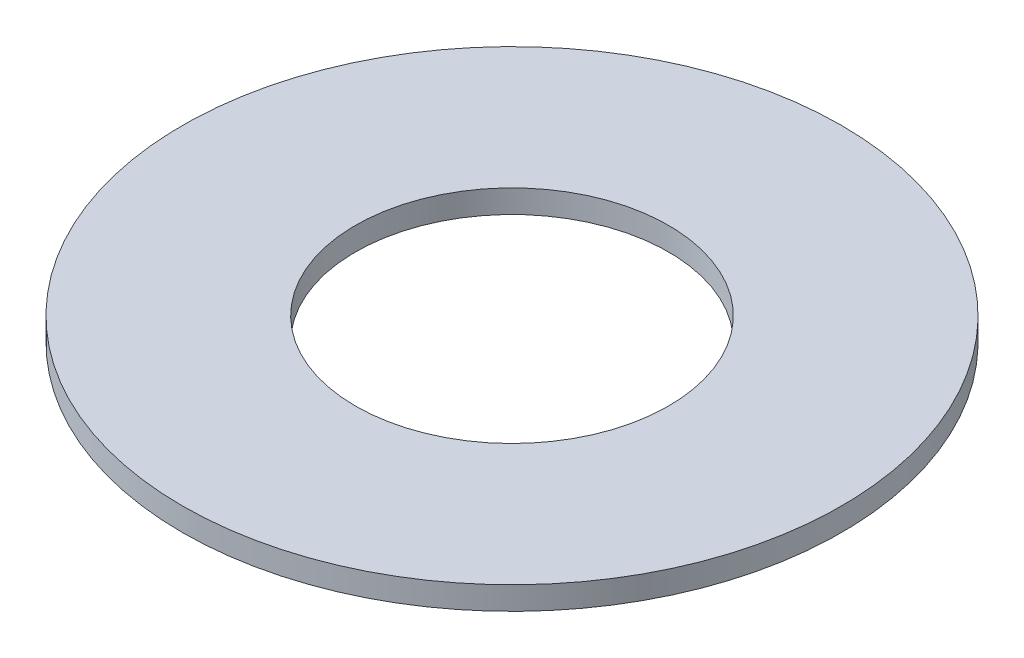
SolidWorks part; units mm, degrees
ref_plane "Front Plane" through (0, 0, 0) normal (0, 0, 1) x (1, 0, 0)
ref_plane "Top Plane" through (0, 0, 0) normal (0, 1, 0) x (1, 0, 0)
ref_plane "Right Plane" through (0, 0, 0) normal (1, 0, 0) x (0, 0, -1)
sketch "Sketch1" plane through (0, 0, 0) normal (0, 1, 0) x (1, 0, 0)
  circle A0 centre (0, 0) radius 100
  dimension "FLANGE_OD" = 200
extrude "Boss-Extrude1" add sketch "Sketch1" along normal blind 7
sketch "Sketch2" plane through (0, 0, 0) normal (0, 1, 0) x (1, 0, 0)
  circle A0 centre (0, 0) radius 47.5
  dimension "BORE_D" = 95
extrude "Cut-Extrude1" cut sketch "Sketch2" along normal through all
sketch "Sketch3" plane through (0, 7, 0) normal (0, 1, 0) x (1, 0, 0)
  circle A0 centre (0, 0) radius 37.662 construction
  circle A1 centre (-37.662, 0) radius 4.657
  dimension "BOLT_D" = 9.314
  dimension "BOLT_PCD" = 75.3239
extrude "Cut-Extrude2" cut sketch "Sketch3" against normal blind 5.8228 rebuild error yes
pattern_circular "CirPattern1" count 4 over 360 rebuild error yes
